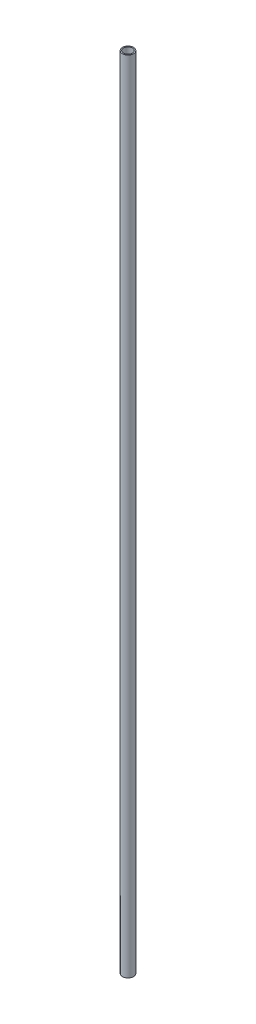
SolidWorks part; units mm, degrees
material "Thornel Mat VMA"
ref_plane "Front Plane" through (0, 0, 0) normal (0, 0, 1) x (1, 0, 0)
ref_plane "Top Plane" through (0, 0, 0) normal (0, 1, 0) x (1, 0, 0)
ref_plane "Right Plane" through (0, 0, 0) normal (1, 0, 0) x (0, 0, -1)
sketch "Sketch1" plane through (0, 0, 0) normal (0, 1, 0) x (1, 0, 0)
  circle A0 centre (0, 0) radius 6.35
  circle A1 centre (0, 0) radius 5.08
  dimension "D1" = 12.7
  dimension "D2" = 1.27
extrude "Boss-Extrude1" add sketch "Sketch1" along normal blind 457.2 and the other way blind 457.2
